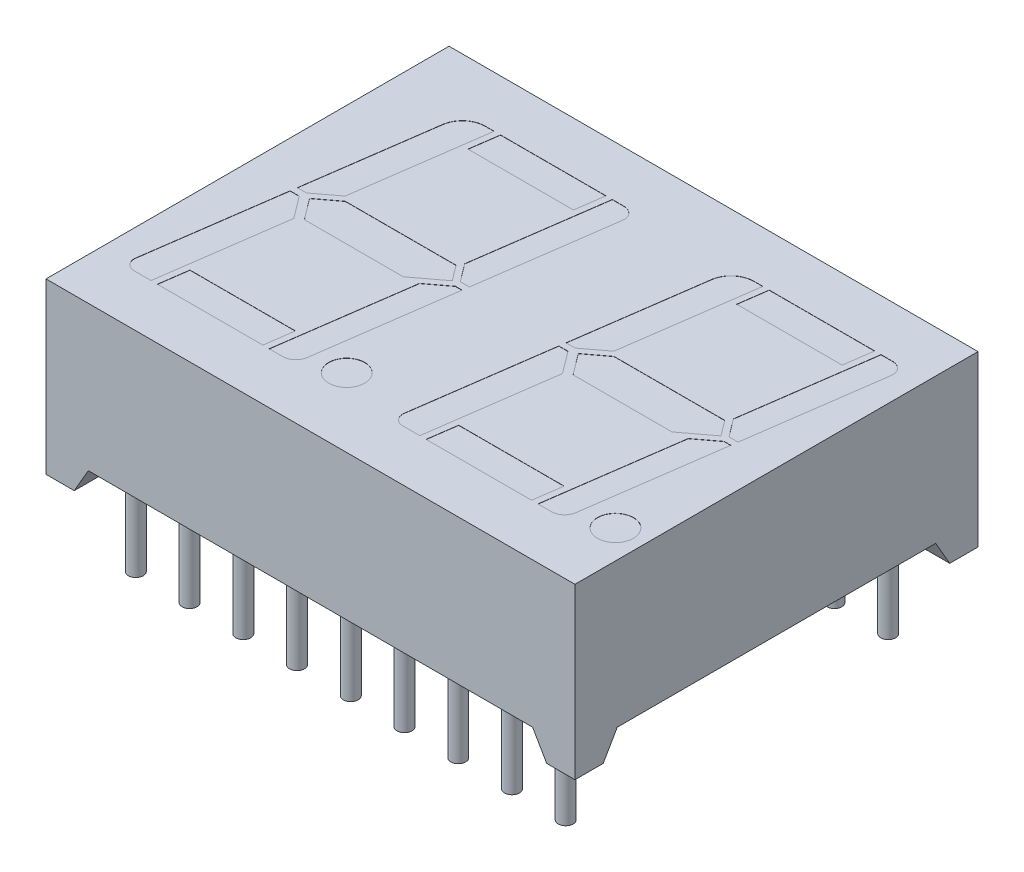
SolidWorks part; units mm, degrees
ref_plane "Front Plane" through (0, 0, 0) normal (0, 0, 1) x (1, 0, 0)
ref_plane "Top Plane" through (0, 0, 0) normal (0, 1, 0) x (1, 0, 0)
ref_plane "Right Plane" through (0, 0, 0) normal (1, 0, 0) x (0, 0, -1)
sketch "Sketch1" plane through (0, 0, 0) normal (0, 1, 0) x (1, 0, 0)
  line L1 (12.5, -9.525) -> (-12.5, -9.525)
  line L2 (12.5, -9.525) -> (12.5, 9.525)
  line L3 (12.5, 9.525) -> (-12.5, 9.525)
  line L4 (-12.5, -9.525) -> (-12.5, 9.525)
  line L5 (12.5, -9.525) -> (-12.5, 9.525) construction
  line L6 (12.5, 9.525) -> (-12.5, -9.525) construction
  point P0 (0, 0)
  dimension "D1" = 19.05
  dimension "D2" = 25
extrude "Boss-Extrude1" add sketch "Sketch1" along normal blind 8
sketch "Sketch2" plane through (0, 0, 9.525) normal (0, 0, 1) x (1, 0, 0)
  line L0 (-11.164, 0) -> (-10.5, 1.15)
  line L1 (-12.5, 0) -> (12.5, 0) construction
  line L2 (-10.5, 1.15) -> (10.5, 1.15)
  line L3 (0, 0) -> (0, 8) construction
  line L4 (-12.5, 8) -> (12.5, 8) construction
  line L5 (11.164, 0) -> (10.5, 1.15)
  line L6 (-12.5, 8) -> (-12.5, 0) construction
  point P12 (0, 1.15)
  dimension "D1" = 2
  dimension "D2" = 120
  dimension "D3" = 1.15
extrude "Cut-Extrude1" cut sketch "Sketch2" along direction (0, 0, 1) on the side against the normal through all
sketch "Sketch3" plane through (0, 8, 0) normal (0, 1, 0) x (1, 0, 0)
  line L0 (0, -9.525) -> (0, 9.525) construction
  line L1 (-12.5, -9.525) -> (12.5, -9.525) construction
  line L2 (12.5, 9.525) -> (-12.5, 9.525) construction
  line L3 (0, 0) -> (-12.5, 0) construction
  line L4 (-3.1842, -7.11) -> (0, -7.11) construction
  line L5 (-12.5, 9.525) -> (-12.5, -9.525) construction
  line L6 (-10.2939, 0.15) -> (-9.4466, 6.1791)
  line L7 (-11.3142, -7.11) -> (-3.1842, -7.11) construction
  line L8 (-11.3142, -7.11) -> (-9.3158, 7.11) construction
  line L9 (-9.3158, 7.11) -> (-1.1858, 7.11) construction
  line L10 (-3.1842, -7.11) -> (-1.1858, 7.11) construction
  line L11 (-11.3142, -7.11) -> (-1.1858, 7.11) construction
  line L12 (-9.3158, 7.11) -> (-3.1842, -7.11) construction
  line L13 (-7.9525, 7.11) -> (-8.8203, 0.9351)
  line L14 (-7.9525, 7.11) -> (-8.3757, 7.11)
  line L15 (-10.2939, 0.15) -> (-9.8622, 0.15)
  line L16 (-9.8622, 0.15) -> (-8.8203, 0.9351)
  line L17 (-6.25, 0.2145) -> (-6.25, 0.8985) construction
  line L18 (-2.3672, 7.11) -> (-1.8135, 7.11)
  line L19 (-7.6525, 7.11) -> (-2.6672, 7.11)
  line L20 (-7.6525, 7.11) -> (-7.8422, 5.76)
  line L21 (-7.8422, 5.76) -> (-2.8569, 5.76)
  line L22 (-2.6672, 7.11) -> (-2.8569, 5.76)
  line L23 (-1.2731, 6.4884) -> (-2.1639, 0.15)
  line L24 (-2.3672, 7.11) -> (-3.2272, 0.9904)
  line L25 (-3.2272, 0.9904) -> (-2.5939, 0.15)
  line L26 (-2.5939, 0.15) -> (-2.1639, 0.15)
  line L27 (-8.6046, 0.7266) -> (-3.37, 0.7266)
  line L28 (-8.6046, 0.7266) -> (-9.5688, 0)
  line L29 (-3.37, 0.7266) -> (-2.8225, 0)
  line L30 (-10.3361, -0.15) -> (-9.9043, -0.15)
  line L31 (-9.9043, -0.15) -> (-9.1192, -1.1919)
  line L32 (-9.1192, -1.1919) -> (-9.951, -7.11)
  line L33 (-9.951, -7.11) -> (-10.7505, -7.11)
  line L34 (-10.3361, -0.15) -> (-11.2358, -6.5517)
  line L35 (-9.8622, 0.15) -> (-9.756, 0.9057) construction
  line L36 (-2.8225, 0) -> (-4.1425, -0.9947)
  line L37 (-9.651, -7.11) -> (-4.6657, -7.11)
  line L38 (-9.651, -7.11) -> (-9.4612, -5.76)
  line L39 (-9.4612, -5.76) -> (-4.4759, -5.76)
  line L40 (-4.6657, -7.11) -> (-4.4759, -5.76)
  line L41 (-4.1425, -0.9947) -> (-8.8192, -0.9947)
  line L42 (-8.8192, -0.9947) -> (-9.5688, 0)
  line L43 (-2.2061, -0.15) -> (-3.1083, -6.5694)
  line L44 (-3.7302, -7.11) -> (-4.3657, -7.11)
  line L45 (-4.3657, -7.11) -> (-3.4899, -0.8786)
  line L46 (-3.4899, -0.8786) -> (-2.523, -0.15)
  line L47 (-2.523, -0.15) -> (-2.2061, -0.15)
  circle A0 centre (-1.55, -6.26) radius 0.85
  arc A1 (-9.4466, 6.1791) -> (-8.3757, 7.11) centre (-8.3757, 6.0286) cw
  arc A2 (-1.8135, 7.11) -> (-1.2731, 6.4884) centre (-1.8135, 6.5643) cw
  arc A3 (-11.2358, -6.5517) -> (-10.7505, -7.11) centre (-10.7505, -6.6199) ccw
  arc A4 (-3.7302, -7.11) -> (-3.1083, -6.5694) centre (-3.7302, -6.482) ccw
  point P12 (-6.25, 0)
  dimension "D1" = 4.7
  dimension "D2" = 14.22
  dimension "D3" = 8.13
  dimension "D4" = 1.35
  dimension "D5" = 8
  dimension "D6" = 135
  dimension "D7" = 0.4318
  dimension "D8" = 0.15
  dimension "D9" = 0.3
  dimension "D10" = 1.35
  dimension "D11" = 0.15
  dimension "D12" = 0.3
  dimension "D13" = 0.43
  dimension "D14" = 135
  dimension "D15" = 0.3
  dimension "D17" = 135
  dimension "D18" = 1.35
  dimension "D19" = 0.3
  dimension "D20" = 0.15
  dimension "D21" = 135
  dimension "D22" = 0.3
  dimension "D24" = 0.15
  dimension "D16" = 0.3
  dimension "D23" = 0.3
extrude "Cut-Extrude3" cut sketch "Sketch3" against normal blind 0.01
pattern_linear "LPattern2" count 2 spacing 12.7 along (1, 0, 0) of "Cut-Extrude3"
sketch "Sketch4" plane through (-12.5, 0, 0) normal (-1, 0, 0) x (0, 0, 1)
  line L0 (-8.189, 0) -> (-7.525, 1.15)
  line L1 (-9.525, 0) -> (9.525, 0) construction
  line L2 (-7.525, 1.15) -> (7.525, 1.15)
  line L3 (0, 0) -> (0, 8) construction
  line L4 (-9.525, 8) -> (9.525, 8) construction
  line L5 (8.189, 0) -> (7.525, 1.15)
  line L6 (-9.525, 8) -> (-9.525, 0) construction
  point P12 (0, 1.15)
  dimension "D1" = 2
  dimension "D2" = 120
  dimension "D3" = 1.15
extrude "Cut-Extrude4" cut sketch "Sketch4" against normal through all
sketch "Sketch5" plane through (0, 1.15, 0) normal (0, -1, 0) x (1, 0, 0)
  line L0 (0, -9.525) -> (0, 9.525) construction
  line L1 (-10.5, -9.525) -> (10.5, -9.525) construction
  line L2 (10.5, 9.525) -> (-10.5, 9.525) construction
  line L3 (-12.5, 0) -> (12.5, 0) construction
  line L4 (-12.5, 7.525) -> (-12.5, -7.525) construction
  line L5 (12.5, -7.525) -> (12.5, 7.525) construction
  circle A0 centre (0, 7.62) radius 0.3509
  circle A1 centre (-2.54, 7.62) radius 0.3509
  circle A2 centre (-5.08, 7.62) radius 0.3509
  circle A3 centre (-7.62, 7.62) radius 0.3509
  circle A4 centre (-10.16, 7.62) radius 0.3509
  circle A5 centre (0, 7.62) radius 0.3509
  circle A6 centre (-2.54, 7.62) radius 0.3509
  circle A7 centre (-5.08, 7.62) radius 0.3509
  circle A8 centre (-7.62, 7.62) radius 0.3509
  circle A9 centre (2.54, 7.62) radius 0.3509
  circle A10 centre (0, 7.62) radius 0.3509
  circle A11 centre (-2.54, 7.62) radius 0.3509
  circle A12 centre (-5.08, 7.62) radius 0.3509
  circle A13 centre (5.08, 7.62) radius 0.3509
  circle A14 centre (2.54, 7.62) radius 0.3509
  circle A15 centre (0, 7.62) radius 0.3509
  circle A16 centre (-2.54, 7.62) radius 0.3509
  circle A17 centre (7.62, 7.62) radius 0.3509
  circle A18 centre (5.08, 7.62) radius 0.3509
  circle A19 centre (2.54, 7.62) radius 0.3509
  circle A20 centre (0, 7.62) radius 0.3509
  circle A21 centre (2.54, 7.62) radius 0.3509
  circle A22 centre (5.08, 7.62) radius 0.3509
  circle A23 centre (7.62, 7.62) radius 0.3509
  circle A24 centre (10.16, 7.62) radius 0.3509
  circle A25 centre (10.16, -7.62) radius 0.3509
  circle A26 centre (7.62, -7.62) radius 0.3509
  circle A27 centre (5.08, -7.62) radius 0.3509
  circle A28 centre (2.54, -7.62) radius 0.3509
  circle A29 centre (-10.16, -7.62) radius 0.3509
  circle A30 centre (-7.62, -7.62) radius 0.3509
  circle A31 centre (-5.08, -7.62) radius 0.3509
  circle A32 centre (-2.54, -7.62) radius 0.3509
  circle A33 centre (0, -7.62) radius 0.3509
  dimension "D1" = 0.7018
  dimension "D4" = 7.62
  dimension "D2" = 5
  dimension "D3" = 5
extrude "Boss-Extrude2" add sketch "Sketch5" along normal blind 4.91 contours A4 | A3 | A2 | A1 | A0 | A9 | A13 | A17 | A24 | A25 | A26 | A27 | A28 | A33 | A32 | A31 | A30 | A29
equation "\"D2@Sketch3\"  =14.22 /2"
equation "\"SegmentSpace\"=0.3"
equation "\"D8@Sketch3\"=\"SegmentSpace\" /2"
equation "\"D9@Sketch3\"=\"SegmentSpace\""
equation "\"SegmentWidth\"=1.35"
equation "\"D4@Sketch3\"=\"SegmentWidth\""
equation "\"D10@Sketch3\"=\"SegmentWidth\""
equation "\"D11@Sketch3\"=\"SegmentSpace\" /2"
equation "\"D12@Sketch3\"=\"SegmentSpace\""
equation "\"D15@Sketch3\"=\"SegmentSpace\""
equation "\"D16@Sketch3\"=\"SegmentSpace\""
equation "\"D18@Sketch3\"=\"SegmentWidth\""
equation "\"D19@Sketch3\"=\"SegmentSpace\""
equation "\"D20@Sketch3\"=\"SegmentSpace\" / 2"
equation "\"D22@Sketch3\"=\"SegmentSpace\""
equation "\"D23@Sketch3\"=\"SegmentSpace\""
equation "\"D24@Sketch3\"=\"SegmentSpace\" /2"
equation "\"D25@Sketch3\" = \"SegmentSpace\""
equation "\"D4@Sketch5\"=15.24 / 2"
